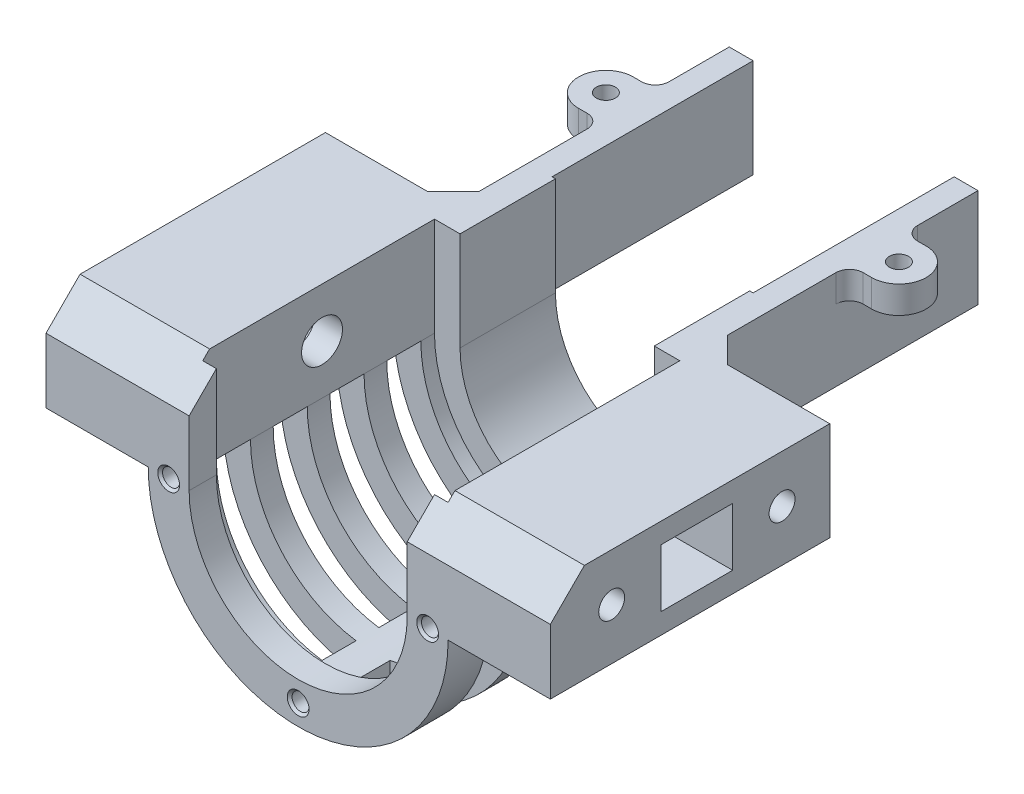
SolidWorks part; units mm, degrees
material "ABS"
ref_plane "前视基准面" through (0, 0, 0) normal (0, 0, 1) x (1, 0, 0)
ref_plane "上视基准面" through (0, 0, 0) normal (0, 1, 0) x (1, 0, 0)
ref_plane "右视基准面" through (0, 0, 0) normal (1, 0, 0) x (0, 0, -1)
sketch "草图1" plane through (0, 0, 0) normal (0, 0, 1) x (1, 0, 0)
  line L1 (-22, -22.5) -> (22, -22.5)
  line L2 (-22, -22.5) -> (-22, 0)
  line L4 (22, -22.5) -> (22, 0)
  line L6 (-22, 0) -> (22, 0)
  dimension "D1" = 44
  dimension "D2" = 22.5
extrude "凸台-拉伸1" add sketch "草图1" along normal blind 52
sketch "草图2" plane through (0, 0, 0) normal (0, 0, -1) x (-1, 0, 0)
  line L0 (22, 0) -> (22, -22.5) construction
  line L5 (-22, 0) -> (22, 0)
  line L6 (-22, 0) -> (-22, -18)
  line L7 (-22, -18) -> (22, -18)
  line L8 (22, 0) -> (22, -18)
  dimension "D1" = 18
extrude "切除-拉伸1" [suppressed] cut sketch "草图2" against normal blind 8
sketch "草图3" plane through (0, 0, 0) normal (0, 1, 0) x (1, 0, 0)
  line L0 (14.25, 0) -> (14.25, -14)
  line L2 (14.25, -14) -> (18, -14)
  line L3 (18, -14) -> (18, -48)
  line L4 (18, -48) -> (16, -48)
  line L5 (16, -48) -> (16, -52)
  line L6 (-22, -52) -> (22, -52) construction
  line L7 (16, -52) -> (0, -52)
  line L8 (0, -52) -> (0, 0)
  line L9 (0, 0) -> (14.25, 0)
  line L10 (0, 8.4743) -> (0, 0) construction
  line L11 (22, -52) -> (42, -52)
  line L17 (22, -52) -> (22, -11)
  line L18 (18.25, 0) -> (42, 0)
  line L19 (42, -52) -> (42, 0)
  line L20 (18.25, 0) -> (18.25, -11)
  line L21 (22, 0) -> (-22, 0) construction
  line L22 (18.25, -11) -> (22, -11)
  dimension "D1" = 28.5
  dimension "D2" = 36
  dimension "D3" = 32
  dimension "D4" = 14
  dimension "D5" = 20
  dimension "D6" = 3
  dimension "D7" = 4
  dimension "D8" = 4
revolve "切除-旋转1" cut sketch "草图3" angle 360 about L10
sketch "草图14" plane through (0, 0, 0) normal (0, 1, 0) x (1, 0, 0)
  line L8 (-14.25, -14) -> (-14.25, 0)
  line L9 (-14.25, 0) -> (-18.25, 0)
  line L11 (-22, -52) -> (-16, -52)
  line L12 (-16, -52) -> (-16, -48)
  line L13 (-16, -48) -> (-18, -48)
  line L14 (-18, -48) -> (-18, -14)
  line L15 (-18, -14) -> (-14.25, -14)
  line L16 (-14.25, -14) -> (-14.25, 0)
  line L17 (-14.25, 0) -> (-18.25, 0)
  line L19 (-22, -52) -> (-16, -52)
  line L20 (-16, -52) -> (-16, -48)
  line L21 (-16, -48) -> (-18, -48)
  line L22 (-18, -48) -> (-18, -14)
  line L23 (-18, -14) -> (-14.25, -14)
  line L24 (14.25, 0) -> (14.25, -14)
  line L25 (14.25, -14) -> (18, -14)
  line L26 (18, -14) -> (18, -48)
  line L27 (18, -48) -> (16, -48)
  line L28 (16, -48) -> (16, -52)
  line L29 (16, -52) -> (22, -52)
  line L31 (18.25, 0) -> (14.25, 0)
  line L32 (14.25, 0) -> (14.25, -14)
  line L33 (14.25, -14) -> (18, -14)
  line L34 (18, -14) -> (18, -48)
  line L35 (18, -48) -> (16, -48)
  line L36 (16, -48) -> (16, -52)
  line L37 (16, -52) -> (22, -52)
  line L39 (18.25, 0) -> (14.25, 0)
  line L40 (-18.25, -11) -> (-22, -11)
  line L41 (-22, -11) -> (-22, -52)
  line L42 (-22, -11) -> (-22, -52)
  line L43 (22, -52) -> (22, -11)
  line L44 (22, -52) -> (22, -11)
  line L45 (-18.25, -11) -> (-22, -11)
  line L46 (-18.25, 0) -> (-18.25, -11)
  line L47 (-18.25, 0) -> (-18.25, -11)
  line L48 (22, -11) -> (18.25, -11)
  line L49 (22, -11) -> (18.25, -11)
  line L50 (18.25, -11) -> (18.25, 0)
  line L51 (18.25, -11) -> (18.25, 0)
  dimension "D1" = 0
  dimension "D2" = 0
extrude "凸台-拉伸2" add sketch "草图14" along normal blind 14.5
sketch "草图15" plane through (0, 0, 0) normal (0, 0, 1) x (1, 0, 0)
  line L0 (0, -20.075) -> (0, 20.075) construction
  line L1 (-18.25, 14.5) -> (-14.75, 14.5)
  line L2 (-18.25, 14.5) -> (-18.25, 0)
  line L3 (-18.25, 0) -> (-14.75, 0)
  line L4 (-14.75, 14.5) -> (-14.75, 0)
  line L5 (14.75, 14.5) -> (14.75, 0)
  line L6 (18.25, 0) -> (14.75, 0)
  line L7 (18.25, 14.5) -> (18.25, 0)
  line L8 (18.25, 14.5) -> (14.75, 14.5)
  arc A1 (-18.25, 0) -> (18.25, 0) centre (0, 0) ccw construction
  dimension "D1" = 29.5
extrude "凸台-拉伸3" add sketch "草图15" against normal blind 29.5
chamfer "倒角1" distance 5 angle 45 2 edges at (19, 14.5, 52) (-19, 14.5, 52)
sketch "草图17" plane through (22, 0, 0) normal (-1, 0, 0) x (0, 0, 1)
  line L6 (18, 7.5) -> (43, 7.5) construction
  line L14 (25.25, 11.5) -> (35.75, 11.5)
  line L15 (25.25, 11.5) -> (25.25, 3)
  line L16 (25.25, 3) -> (35.75, 3)
  line L17 (35.75, 11.5) -> (35.75, 3)
  line L18 (52, 0) -> (52, 9.5)
  line L19 (52, 9.5) -> (47, 14.5)
  line L20 (47, 14.5) -> (11, 14.5)
  line L21 (11, 14.5) -> (11, 0)
  line L22 (11, 0) -> (52, 0)
  line L23 (52, 0) -> (52, 9.5)
  line L24 (52, 9.5) -> (47, 14.5)
  line L25 (47, 14.5) -> (11, 14.5)
  line L26 (11, 14.5) -> (11, 0)
  line L27 (11, 0) -> (52, 0)
  circle A0 centre (18, 7.5) radius 1.9
  circle A1 centre (43, 7.5) radius 1.9
  dimension "D2" = 3.8
  dimension "D5" = 7
  dimension "D6" = 7.25
  dimension "D1" = 0
  dimension "D3" = 25
  dimension "D4" = 7.5
  dimension "D7" = 7.25
  dimension "D8" = 3
  dimension "D9" = 3
extrude "凸台-拉伸5" add sketch "草图17" against normal blind 15
sketch "草图13" plane through (0, 0, 0) normal (1, 0, 0) x (0, 0, -1)
  line L0 (-52, -22) -> (-11, -22) construction
  line L1 (-46, 0) -> (-41, 0)
  line L2 (-46, 0) -> (-46, -22)
  line L3 (-46, -22) -> (-41, -22)
  line L4 (-41, 0) -> (-41, -22)
  line L5 (-52, 0) -> (-11, 0) construction
  line L6 (-35.75, 11.5) -> (-25.25, 3) construction
  line L7 (-37.6667, 0) -> (-32.6667, 0)
  line L8 (-37.6667, 0) -> (-37.6667, -22)
  line L9 (-37.6667, -22) -> (-32.6667, -22)
  line L10 (-32.6667, 0) -> (-32.6667, -22)
  line L11 (-29.3333, 0) -> (-24.3333, 0)
  line L12 (-29.3333, 0) -> (-29.3333, -22)
  line L13 (-29.3333, -22) -> (-24.3333, -22)
  line L14 (-24.3333, 0) -> (-24.3333, -22)
  line L15 (-21, 0) -> (-16, 0)
  line L16 (-21, 0) -> (-21, -22)
  line L17 (-21, -22) -> (-16, -22)
  line L18 (-16, 0) -> (-16, -22)
  line L29 (-48, -18) -> (-48, 0) construction
  line L30 (-14, 0) -> (-14, -18) construction
  circle A0 centre (-30.5, 7.25) radius 3
  dimension "D4" = 6
  dimension "D1" = 2
  dimension "D2" = 2
  dimension "D3" = 4
  dimension "D5" = 5
extrude "切除-拉伸10" cut sketch "草图13" along normal through all from offset 2.5
mirror "镜向1" about plane through (0, 0, 0) normal (1, 0, 0) of "凸台-拉伸5", "切除-拉伸10"
sketch "草图21" plane through (0, 0, 0) normal (0, -1, 0) x (1, 0, 0)
  line L0 (0, -20.075) -> (0, 20.075) construction
  line L1 (33, 47.25) -> (22, 47.25)
  line L2 (33, 47.25) -> (33, 38.75)
  line L3 (33, 38.75) -> (22, 38.75)
  line L4 (22, 47.25) -> (22, 38.75)
  line L6 (37, 11) -> (37, 52) construction
  line L7 (-22, 22.25) -> (-22, 13.75)
  line L8 (29.5, 41.1) -> (29.5, 44.9) construction
  line L9 (22, 41.1) -> (37, 41.1) construction
  line L10 (37, 44.9) -> (22, 44.9) construction
  line L11 (22, 43) -> (29.5, 43) construction
  line L12 (33, 22.25) -> (22, 22.25)
  line L13 (33, 22.25) -> (33, 13.75)
  line L14 (33, 13.75) -> (22, 13.75)
  line L15 (22, 22.25) -> (22, 13.75)
  line L16 (29.5, 16.1) -> (29.5, 19.9) construction
  line L18 (22, 16.1) -> (37, 16.1) construction
  line L19 (37, 19.9) -> (22, 19.9) construction
  line L20 (22, 18) -> (29.5, 18) construction
  line L27 (-22, 47.25) -> (-22, 38.75)
  line L28 (-33, 38.75) -> (-22, 38.75)
  line L29 (-33, 47.25) -> (-33, 38.75)
  line L30 (-33, 47.25) -> (-22, 47.25)
  line L31 (-33, 13.75) -> (-22, 13.75)
  line L32 (-33, 22.25) -> (-33, 13.75)
  line L33 (18, 14) -> (18, 47) construction
  line L34 (-33, 22.25) -> (-22, 22.25)
  dimension "D1" = 8.5
  dimension "D2" = 4
  dimension "D3" = 4
  dimension "D4" = 2
extrude "切除-拉伸12" cut sketch "草图21" against normal blind 11.2
hole_wizard "M3 螺纹孔1" positions "草图18" profile "草图20" tap size "M3" standard "GB"
sketch "草图18" plane through (0, 0, 52) normal (0, 0, 1) x (1, 0, 0)
  circle A0 centre (0, 0) radius 19 construction
  arc A1 (-22, 0) -> (22, 0) centre (0, 0) ccw construction
  point P0 (-19, 0)
  point P2 (0, -19)
  point P4 (19, 0)
  dimension "D1" = 3
sketch "草图20" plane through (-19, 0, 52) normal (1, 0, 0) x (0, -1, 0)
  line L0 (0, 0) -> (0, 4.7501)
  line L1 (0, 4.7501) -> (1.25, 3.999)
  line L2 (1.25, 3.999) -> (1.25, 0.35)
  line L3 (1.25, 0.35) -> (1.6, 0)
  line L5 (1.6, 0) -> (0, 0)
  line L6 (-1.25, 0.35) -> (-1.6, 0) construction
  line L10 (0, 4.7501) -> (-1.25, 3.999) construction
  line L11 (0, -6.35) -> (0, 107.95) construction
  dimension "螺纹孔钻头直径" = 2.5
  dimension "螺纹孔钻头深度" = 3.999
  dimension "近端锥形沉头孔直径" = 3.2
  dimension "近端锥形沉头孔角度" = 90
  dimension "导头角度" = 118
sketch "草图23" plane through (0, 14.5, 0) normal (0, 1, 0) x (1, 0, 0)
  line L0 (-18.25, 18.65) -> (-21.5, 18.65)
  line L1 (-18.25, 29.5) -> (-18.25, -11) construction
  line L2 (-18.25, 10.65) -> (-21.5, 10.65)
  line L3 (-18.25, 10.65) -> (-18.25, 18.65)
  line L4 (14.25, 0) -> (-14.25, 0) construction
  line L5 (0, -20.075) -> (0, 20.075) construction
  line L6 (18.25, 10.65) -> (18.25, 18.65)
  line L7 (18.25, 10.65) -> (21.5, 10.65)
  line L8 (18.25, 18.65) -> (21.5, 18.65)
  circle A1 centre (-21.5, 14.65) radius 1.4
  arc A2 (-21.5, 18.65) -> (-21.5, 10.65) centre (-21.5, 14.65) ccw
  arc A3 (21.5, 18.65) -> (21.5, 10.65) centre (21.5, 14.65) cw
  circle A4 centre (21.5, 14.65) radius 1.4
  dimension "D1" = 2.8
  dimension "D2" = 14.65
  dimension "D3" = 43
  dimension "D4" = 4
extrude "凸台-拉伸7" add sketch "草图23" against normal blind 4
fillet "圆角2" radius 2 4 edges at (-18.25, 12.5, -10.65) (-18.25, 12.5, -18.65) (18.25, 12.5, -18.65) (18.25, 12.5, -10.65)
chamfer "倒角3" distance 3.75 angle 45 3 edges at (18.25, 7.25, 11) (-18.25, 7.25, 11) (0, -18.25, 11)
